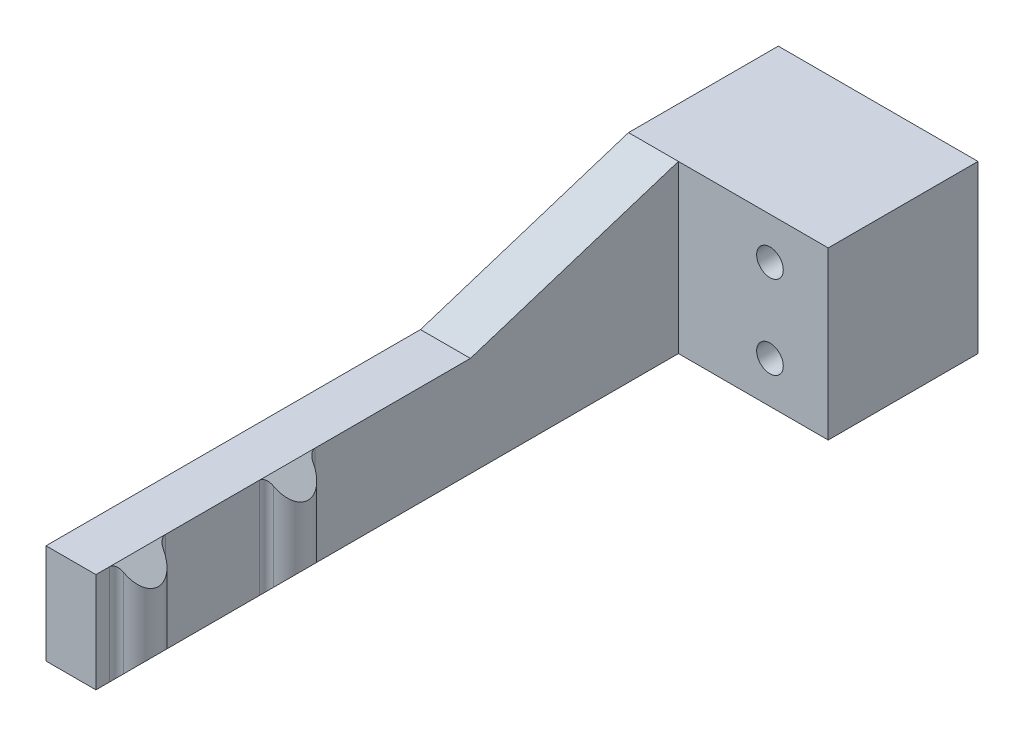
SolidWorks part; units mm, degrees
material "PLA+"
ref_plane "Front Plane" through (0, 0, 0) normal (0, 0, 1) x (1, 0, 0)
ref_plane "Top Plane" through (0, 0, 0) normal (0, 1, 0) x (1, 0, 0)
ref_plane "Right Plane" through (0, 0, 0) normal (1, 0, 0) x (0, 0, -1)
sketch "Sketch1" plane through (0, 0, 0) normal (0, 0, 1) x (1, 0, 0)
  line L1 (-12, -10) -> (12, -10)
  line L2 (-12, -10) -> (-12, 10)
  line L3 (-12, 10) -> (12, 10)
  line L4 (12, -10) -> (12, 10)
  line L5 (-12, -10) -> (12, 10) construction
  line L6 (-12, 10) -> (12, -10) construction
  point P0 (0, 0)
  dimension "D1" = 24
  dimension "D2" = 20
extrude "Boss-Extrude1" add sketch "Sketch1" along normal blind 18
sketch "Sketch2" plane through (0, 0, 18) normal (0, 0, 1) x (1, 0, 0)
  line L0 (12, 10) -> (-12, 10) construction
  line L2 (12, -10) -> (12, 10) construction
  circle A0 centre (5, 5) radius 1.6
  circle A1 centre (5, -5) radius 1.6
  dimension "D1" = 3.2
  dimension "D2" = 3.2
  dimension "D4" = 5
  dimension "D3" = 10
  dimension "D5" = 7
extrude "Cut-Extrude1" cut sketch "Sketch2" against normal through all
sketch "Sketch3" plane through (-12, 0, 0) normal (-1, 0, 0) x (0, 0, 1)
  line L0 (18, 10) -> (18, -10) construction
  line L1 (18, 2) -> (88, 2) construction
  line L2 (18, 2) -> (18, -10)
  line L3 (18, -10) -> (88, -10)
  line L4 (88, 2) -> (88, -10)
  line L5 (18, -10) -> (0, -10) construction
  line L6 (18, 10) -> (43, 2)
  line L7 (43, 2) -> (88, 2)
  line M7 (18, -10) -> (18, 10)
  dimension "D1" = 12
  dimension "D2" = 70
  dimension "D3" = 25
extrude "Boss-Extrude2" add sketch "Sketch3" against normal blind 6 contours L1 L3 L4 L7 M7 | L1 L6 M7 region at (-12, 4.6667, 26.3333) region at (-12, -4, 53)
ref_plane "Plane1" through (0, -7.5, 0) normal (0, -1, 0) x (-1, 0, 0)
sketch "Sketch4" plane through (0, -7.5, 0) normal (0, -1, 0) x (-1, 0, 0)
  line L0 (6, -43) -> (6, -88) construction
  line L1 (6, -88) -> (12, -88) construction
  line L2 (-12, -9) -> (-23.3005, -9) construction
  line L3 (-12, -18) -> (-12, 0) construction
  circle A0 centre (6, -83) radius 2.5
  circle A1 centre (6, -65) radius 2.5
  circle A2 centre (-40.6396, -74) radius 45 construction
  dimension "D1" = 5
  dimension "D3" = 5
  dimension "D4" = 90
  dimension "D2" = 5
  dimension "D5" = 65
extrude "Boss-Extrude3" add sketch "Sketch4" against normal blind 7
fillet "Fillet1" radius 1 4 edges at (-6, -4, 85.5) (-6, -4, 67.5) (-6, -4, 62.5) (-6, -4, 80.5)
chamfer "Chamfer2" distance 2.5 angle 45 4 edges at (-6, -0.5, 83) (-6, -0.5, 65) (-6, -7.5, 65) (-6, -7.5, 83)
